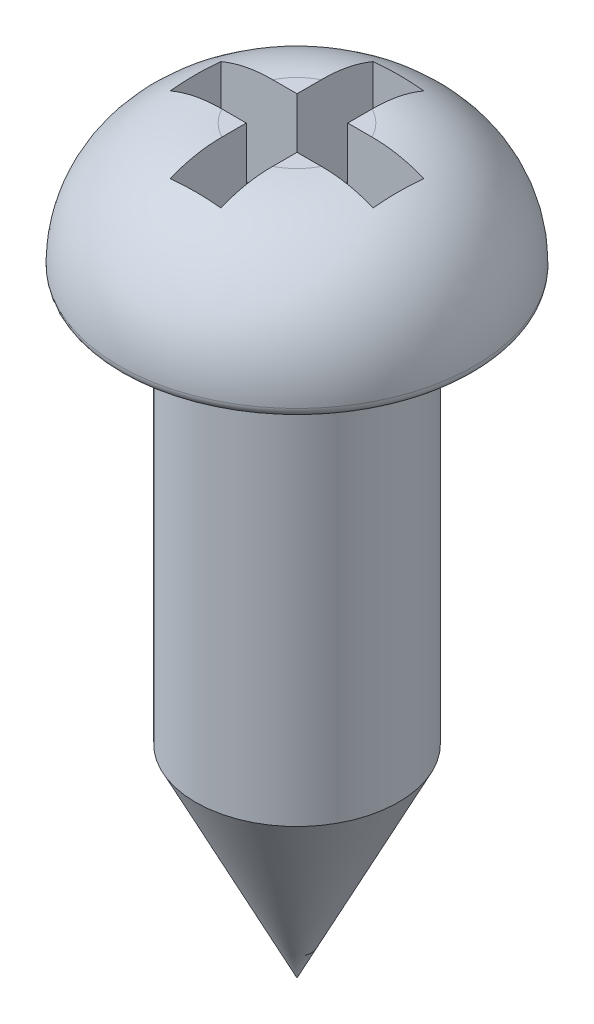
SolidWorks part; units mm, degrees
material "Plain Carbon Steel"
ref_plane "Front Plane" through (0, 0, 0) normal (0, 0, 1) x (1, 0, 0)
ref_plane "Top Plane" through (0, 0, 0) normal (0, 1, 0) x (1, 0, 0)
ref_plane "Right Plane" through (0, 0, 0) normal (1, 0, 0) x (0, 0, -1)
sketch "Sketch1" plane through (0, 0, 0) normal (0, 1, 0) x (1, 0, 0)
  circle A0 centre (0, 0) radius 1
  dimension "D1" = 2
extrude "Boss-Extrude1" add sketch "Sketch1" along normal blind 6
sketch "Sketch2" plane through (0, 6, 0) normal (0, 1, 0) x (1, 0, 0)
  circle A0 centre (0, 0) radius 1.75
  dimension "D1" = 3.5
extrude "Boss-Extrude2" add sketch "Sketch2" along normal blind 1.3
sketch "Sketch3" plane through (0, 7.3, 0) normal (0, 1, 0) x (1, 0, 0)
  line L0 (-1.75, 0) -> (1.75, 0) construction
  line L1 (0, 1.75) -> (0, -1.75) construction
  line L2 (-1, -0.25) -> (-1, 0.25)
  line L3 (-1, 0.25) -> (-0.25, 0.25)
  line L4 (-0.25, 0.25) -> (-0.25, 1)
  line L5 (-0.25, 1) -> (0.25, 1)
  line L6 (-0.25, -1) -> (0.25, -1)
  line L7 (-0.25, -0.25) -> (-0.25, -1)
  line L8 (-1, -0.25) -> (-0.25, -0.25)
  line L9 (1, -0.25) -> (0.25, -0.25)
  line L10 (0.25, -0.25) -> (0.25, -1)
  line L11 (0.25, 0.25) -> (0.25, 1)
  line L12 (1, 0.25) -> (0.25, 0.25)
  line L13 (1, -0.25) -> (1, 0.25)
  circle A0 centre (0, 0) radius 1.75 construction
  point P16 (-1, 0)
  point P19 (0, -1)
  point P20 (0, 1)
  point P22 (1, 0)
  dimension "D1" = 0.25
  dimension "D2" = 0.25
  dimension "D3" = 1
  dimension "D4" = 1
extrude "Cut-Extrude1" cut sketch "Sketch3" against normal blind 1
fillet "Fillet1" radius 1.2 1 edges at (0, 7.3, 1.75)
fillet "Fillet2" radius 0.1 1 edges at (0, 6, 1.75)
chamfer "Chamfer1" distance 1 distance2 2 1 edges at (0, 0, 1) first distance on face at (0, 0, 1)
